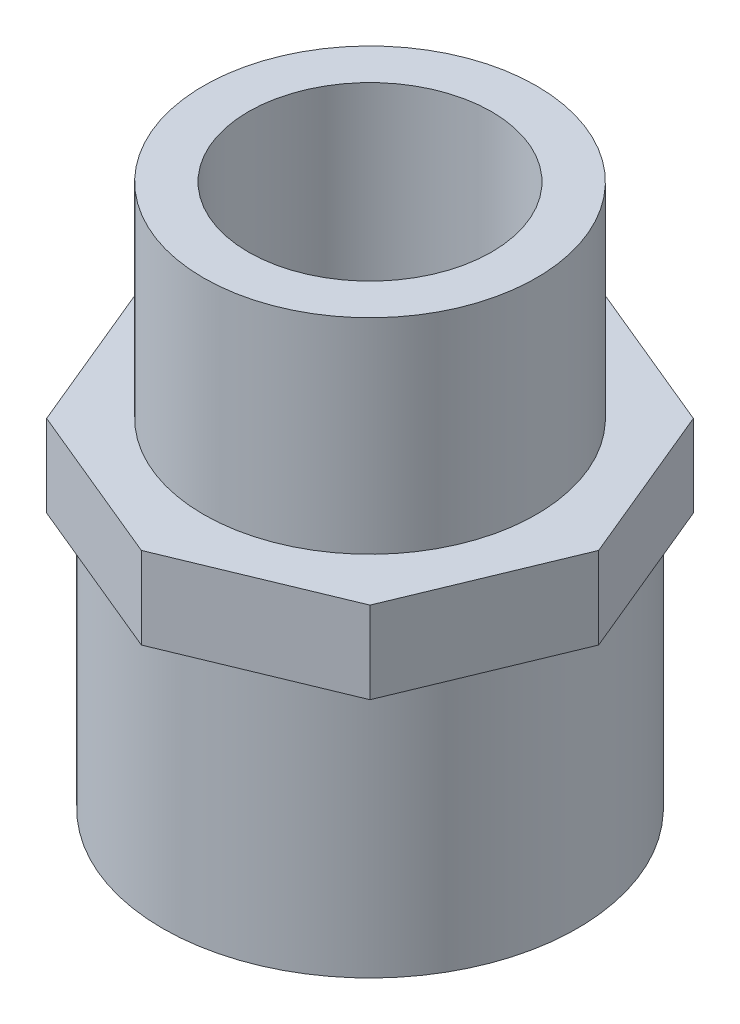
SolidWorks part; units mm, degrees
material "PVC Rigid"
ref_plane "Front Plane" through (0, 0, 0) normal (0, 0, 1) x (1, 0, 0)
ref_plane "Top Plane" through (0, 0, 0) normal (0, 1, 0) x (1, 0, 0)
ref_plane "Right Plane" through (0, 0, 0) normal (1, 0, 0) x (0, 0, -1)
sketch "Sketch1" plane through (0, 0, 0) normal (0, 1, 0) x (1, 0, 0)
  line L1 (22.6815, 0) -> (16.0383, 16.0383)
  line L2 (16.0383, 16.0383) -> (0, 22.6815)
  line L3 (0, 22.6815) -> (-16.0383, 16.0383)
  line L4 (-16.0383, 16.0383) -> (-22.6815, 0)
  line L5 (-22.6815, 0) -> (-16.0383, -16.0383)
  line L6 (-16.0383, -16.0383) -> (0, -22.6815)
  line L7 (0, -22.6815) -> (16.0383, -16.0383)
  line L8 (16.0383, -16.0383) -> (22.6815, 0)
  circle A0 centre (0, 0) radius 20.955 construction
  circle A1 centre (0, 0) radius 12.065
  dimension "D1" = 41.91
  dimension "D2" = 24.13
extrude "Boss-Extrude1" add sketch "Sketch1" along normal blind 8.128
sketch "Sketch2" plane through (0, 0, 0) normal (0, -1, 0) x (1, 0, 0)
  circle A0 centre (0, 0) radius 16.637
  circle A1 centre (0, 0) radius 20.574
  dimension "D1" = 41.148
  dimension "D2" = 33.274
extrude "Boss-Extrude2" add sketch "Sketch2" along normal blind 25.4
sketch "Sketch3" plane through (0, 8.128, 0) normal (0, 1, 0) x (1, 0, 0)
  circle A0 centre (0, 0) radius 12.065
  circle A1 centre (0, 0) radius 16.51
  dimension "D1" = 33.02
  dimension "D2" = 24.13
extrude "Boss-Extrude3" add sketch "Sketch3" along normal blind 20.32
